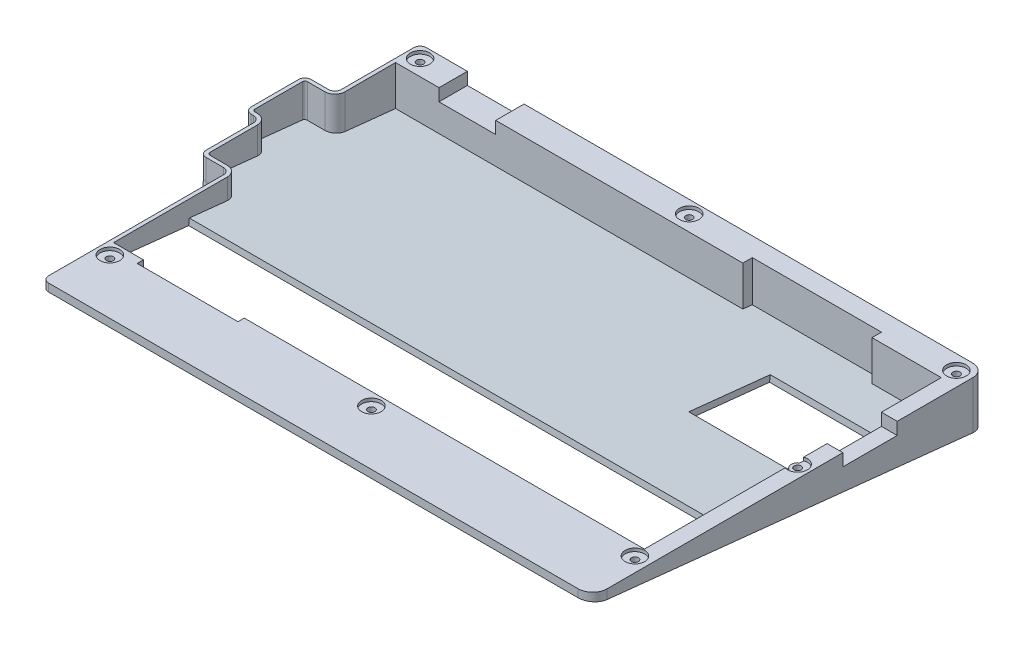
SolidWorks part; units mm, degrees
ref_plane "Front Plane" through (0, 0, 0) normal (0, 0, 1) x (1, 0, 0)
ref_plane "Top Plane" through (0, 0, 0) normal (0, 1, 0) x (1, 0, 0)
ref_plane "Right Plane" through (0, 0, 0) normal (1, 0, 0) x (0, 0, -1)
sketch "Sketch1" plane through (0, 0, 0) normal (0, 1, 0) x (1, 0, 0)
  line L0 (138.4196, 31.7518) -> (125.4196, 31.7518)
  line L1 (-35.0204, 31.7518) -> (107.4196, 31.7518)
  line L2 (140.4196, 29.7518) -> (140.4196, 6.7018)
  line L3 (-34.0204, 3.7518) -> (-34.0204, 22.7518)
  line L4 (136.4596, 27.7518) -> (136.4396, 27.7518)
  line L5 (142.4196, 4.7018) -> (147.9496, 4.7018)
  line L6 (-34.0204, 22.7518) -> (-12.0204, 22.7518)
  line L8 (149.9496, 2.7018) -> (149.9496, -12.3482)
  line L11 (147.9496, -14.3482) -> (147.1896, -14.3482)
  line L14 (145.1896, -16.3482) -> (145.1896, -31.3982)
  line L17 (143.1896, -33.3982) -> (137.6696, -33.3982)
  line L20 (135.6696, -35.3982) -> (135.6696, -77.4982)
  line L21 (-34.0204, -25.6003) -> (-34.0204, -71.4982)
  line L23 (133.6696, -79.4982) -> (-35.0204, -79.4982)
  line L28 (-39.0204, 27.7518) -> (-39.0204, 3.7518)
  line L31 (-34.0204, 3.7518) -> (-39.0204, 3.7518)
  line L32 (-34.0204, -13.4982) -> (-39.0204, -13.4982)
  line L33 (-39.0204, -75.4982) -> (-39.0204, -13.4982)
  line L34 (-34.0204, -71.4982) -> (92.9796, -71.4982)
  line L35 (92.9796, -71.4982) -> (92.9796, -73.4982)
  line L36 (92.9796, -73.4982) -> (124.9796, -73.4982)
  line L37 (124.9796, -73.4982) -> (124.9796, -71.4982)
  line L39 (134.4706, -35.3982) -> (134.4706, -71.4982)
  line L40 (134.4706, -71.4982) -> (124.9796, -71.4982)
  line L41 (137.6696, -32.1992) -> (143.1896, -32.1992)
  line L42 (-34.0204, -13.4982) -> (-34.0204, -22.1362)
  line L43 (143.9906, -31.3982) -> (143.9906, -16.3482)
  line L44 (-12.0204, 22.7518) -> (-12.0204, 25.7518)
  line L45 (147.1896, -13.1492) -> (147.9496, -13.1492)
  line L46 (148.7506, -12.3482) -> (148.7506, 2.7018)
  line L47 (-12.0204, 25.7518) -> (28.9796, 25.7518)
  line L48 (28.9796, 25.7518) -> (28.9796, 22.7518)
  line L49 (28.9796, 22.7518) -> (107.4196, 22.7518)
  line L50 (147.9496, 3.5027) -> (142.4196, 3.5027)
  line L51 (107.4196, 22.7518) -> (107.4196, 31.7518)
  line L52 (139.2206, 6.7018) -> (139.2206, 22.7518)
  line L53 (125.4196, 31.7518) -> (125.4196, 22.7518)
  line L54 (139.2206, 22.7518) -> (125.4196, 22.7518)
  arc A0 (138.4196, 31.7518) -> (140.4196, 29.7518) centre (138.4196, 29.7518) cw
  arc A1 (140.4196, 6.7018) -> (142.4196, 4.7018) centre (142.4196, 6.7018) ccw
  arc A2 (149.9496, 2.7018) -> (147.9496, 4.7018) centre (147.9496, 2.7018) ccw
  arc A3 (149.9496, -12.3482) -> (147.9496, -14.3482) centre (147.9496, -12.3482) cw
  arc A4 (147.1896, -14.3482) -> (145.1896, -16.3482) centre (147.1896, -16.3482) ccw
  arc A5 (145.1896, -31.3982) -> (143.1896, -33.3982) centre (143.1896, -31.3982) cw
  arc A6 (-35.0204, 31.7518) -> (-39.0204, 27.7518) centre (-35.0204, 27.7518) ccw
  arc A7 (-39.0204, -75.4982) -> (-35.0204, -79.4982) centre (-35.0204, -75.4982) ccw
  arc A8 (133.6696, -79.4982) -> (135.6696, -77.4982) centre (133.6696, -77.4982) ccw
  arc A9 (135.6696, -35.3982) -> (137.6696, -33.3982) centre (137.6696, -35.3982) cw
  circle A10 centre (-34.4204, 27.1518) radius 1.1
  circle A11 centre (51.0096, 27.7518) radius 1.1
  circle A12 centre (136.4396, 27.7518) radius 1.1
  circle A13 centre (-34.4204, -74.8982) radius 1.1
  circle A14 centre (48.6296, -75.4982) radius 1.1
  circle A15 centre (131.6496, -75.4982) radius 1.1
  circle A16 centre (-35.0204, -23.8682) radius 1.1
  arc A27 (-34.0204, -22.1362) -> (-34.0204, -25.6003) centre (-35.0204, -23.8682) cw
  arc A28 (139.2206, 6.7018) -> (142.4196, 3.5027) centre (142.4196, 6.7018) ccw
  arc A29 (147.9496, 3.5027) -> (148.7506, 2.7018) centre (147.9496, 2.7018) cw
  arc A30 (148.7506, -12.3482) -> (147.9496, -13.1492) centre (147.9496, -12.3482) cw
  arc A31 (147.1896, -13.1492) -> (143.9906, -16.3482) centre (147.1896, -16.3482) ccw
  arc A32 (143.9906, -31.3982) -> (143.1896, -32.1992) centre (143.1896, -31.3982) cw
  arc A33 (137.6696, -32.1992) -> (134.4706, -35.3982) centre (137.6696, -35.3982) ccw
extrude "Boss-Extrude2" add sketch "Sketch1" against normal blind 4.7 contours L41 A33 L39 L40 L37 L36 L35 L34 L21 A27 L42 L32 L33 A7 L23 A8 L20 A9 L17 A5 L14 A4 L11 A3 L8 A2 L5 A1 L2 A0 L0 L53 L54 L52 A28 L50 A29 L46 A30 L45 A31 L43 A32 A12 A13 A14 A15 | L1 A6 L28 L31 L3 L6 L44 L47 L48 L49 L51 A11 A10 region at (138.2833, 0, -29.6154) region at (31.7683, 0, -26.4895)
move or copy body "Body-Move/Copy1" bodies to move or copy 105 104 copy no rotation origin (55.4646, -2.35, 0) rotation axis (0, 0, 1) rotation angle 180
sketch "Sketch3" plane through (149.9496, 0, 0) normal (1, 0, 0) x (0, 0, -1)
  line L0 (-79.4982, 0) -> (-79.4982, -4.7) construction
  line L1 (-79.4982, 0) -> (-79.4982, -4.7)
  line L2 (31.7518, 0) -> (31.7518, -4.7) construction
  line L3 (31.7518, 0) -> (31.7518, -4.7)
  line L5 (-79.4982, -4.7) -> (31.7518, -16.3928)
  line L6 (31.7518, -16.3928) -> (31.7518, -4.7)
  line L7 (31.7518, -4.7) -> (-79.4982, -4.7)
  line M3 (-75.4982, -4.7) -> (-13.4982, -4.7)
  dimension "D1" = 6
extrude "Boss-Extrude3" add sketch "Sketch3" against normal up to surface (188.97 mm away) contours L6 L7 L5 M3 region at (149.9496, -8.5976, 5.3315) up to face at (-39.0204, -2.35, 4.8232)
sketch "Sketch4" plane through (0, -4.7, 0) normal (0, 1, 0) x (1, 0, 0)
  line L2 (145.9496, -79.4982) -> (149.9496, -79.4982)
  line L3 (149.9496, -79.4982) -> (149.9496, -75.4982)
  line L4 (-29.4904, 6.7018) -> (-29.4904, 29.7518)
  line L5 (-27.4904, 31.7518) -> (-39.0204, 31.7518)
  line L6 (-36.2604, -14.3482) -> (-37.0204, -14.3482)
  line L7 (-39.0204, -12.3482) -> (-39.0204, -79.4982)
  line L8 (-39.0204, -79.4982) -> (-22.7404, -79.4982)
  line L9 (-24.7404, -77.4982) -> (-24.7404, -35.3982)
  line L10 (-26.7404, -33.3982) -> (-32.2604, -33.3982)
  line L11 (-34.2604, -31.3982) -> (-34.2604, -16.3482)
  line L12 (-36.2604, -14.3482) -> (-37.0204, -14.3482)
  line L13 (-39.0204, -12.3482) -> (-39.0204, -79.4982)
  line L14 (-39.0204, -79.4982) -> (-22.7404, -79.4982)
  line L15 (-24.7404, -77.4982) -> (-24.7404, -35.3982)
  line L16 (-26.7404, -33.3982) -> (-32.2604, -33.3982)
  line L17 (-34.2604, -31.3982) -> (-34.2604, -16.3482)
  line L18 (-39.0204, 31.7518) -> (-39.0204, 2.7018)
  line L19 (-37.0204, 4.7018) -> (-31.4904, 4.7018)
  line L20 (-29.4904, 6.7018) -> (-29.4904, 29.7518)
  line L21 (-27.4904, 31.7518) -> (-39.0204, 31.7518)
  line L22 (-39.0204, 31.7518) -> (-39.0204, 2.7018)
  line L23 (-37.0204, 4.7018) -> (-31.4904, 4.7018)
  line L24 (145.9496, -79.4982) -> (149.9496, -79.4982)
  line L25 (149.9496, -79.4982) -> (149.9496, -75.4982)
  line L26 (149.9496, 31.7518) -> (145.9496, 31.7518)
  line L27 (149.9496, 27.7518) -> (149.9496, 31.7518)
  line L28 (149.9496, 31.7518) -> (145.9496, 31.7518)
  line L29 (149.9496, 27.7518) -> (149.9496, 31.7518)
  arc A1 (145.9496, -79.4982) -> (149.9496, -75.4982) centre (145.9496, -75.4982) ccw
  arc A2 (145.9496, -79.4982) -> (149.9496, -75.4982) centre (145.9496, -75.4982) ccw
  arc A3 (-27.4904, 31.7518) -> (-29.4904, 29.7518) centre (-27.4904, 29.7518) ccw
  arc A4 (-37.0204, 4.7018) -> (-39.0204, 2.7018) centre (-37.0204, 2.7018) ccw
  arc A5 (-39.0204, -12.3482) -> (-37.0204, -14.3482) centre (-37.0204, -12.3482) ccw
  arc A6 (-24.7404, -77.4982) -> (-22.7404, -79.4982) centre (-22.7404, -77.4982) ccw
  arc A7 (-24.7404, -35.3982) -> (-26.7404, -33.3982) centre (-26.7404, -35.3982) ccw
  arc A8 (-34.2604, -31.3982) -> (-32.2604, -33.3982) centre (-32.2604, -31.3982) ccw
  arc A9 (-34.2604, -16.3482) -> (-36.2604, -14.3482) centre (-36.2604, -16.3482) ccw
  arc A10 (-39.0204, -12.3482) -> (-37.0204, -14.3482) centre (-37.0204, -12.3482) ccw
  arc A11 (-24.7404, -77.4982) -> (-22.7404, -79.4982) centre (-22.7404, -77.4982) ccw
  arc A12 (-24.7404, -35.3982) -> (-26.7404, -33.3982) centre (-26.7404, -35.3982) ccw
  arc A13 (-34.2604, -31.3982) -> (-32.2604, -33.3982) centre (-32.2604, -31.3982) ccw
  arc A14 (-34.2604, -16.3482) -> (-36.2604, -14.3482) centre (-36.2604, -16.3482) ccw
  arc A15 (-31.4904, 4.7018) -> (-29.4904, 6.7018) centre (-31.4904, 6.7018) ccw
  arc A16 (-27.4904, 31.7518) -> (-29.4904, 29.7518) centre (-27.4904, 29.7518) ccw
  arc A17 (-37.0204, 4.7018) -> (-39.0204, 2.7018) centre (-37.0204, 2.7018) ccw
  arc A18 (-31.4904, 4.7018) -> (-29.4904, 6.7018) centre (-31.4904, 6.7018) ccw
  arc A19 (149.9496, 27.7518) -> (145.9496, 31.7518) centre (145.9496, 27.7518) ccw
  arc A20 (149.9496, 27.7518) -> (145.9496, 31.7518) centre (145.9496, 27.7518) ccw
  dimension "D1" = 0
  dimension "D2" = 0
  dimension "D3" = 0
  dimension "D4" = 0
extrude "Cut-Extrude1" cut sketch "Sketch4" against normal through all
ref_plane "Plane4" through (0, 15, 0) normal (0, 1, 0) x (1, 0, 0)
sketch "Sketch10" plane through (0, 15, 0) normal (0, 1, 0) x (1, 0, 0)
  line L0 (-14.4904, 22.7518) -> (3.5096, 22.7518)
  line L1 (144.9496, 3.7518) -> (144.9496, -13.4982)
  line L27 (-14.4904, 31.7518) -> (-14.4904, 22.7518)
  line L28 (-14.4904, 22.7518) -> (-28.2913, 22.7518)
  line L29 (-28.2913, 22.7518) -> (-28.2913, 6.7018)
  line L30 (-31.4904, 3.5027) -> (-37.0204, 3.5027)
  line L31 (-37.8213, 2.7018) -> (-37.8213, -12.3482)
  line L32 (-37.0204, -13.1492) -> (-36.2604, -13.1492)
  line L33 (-33.0613, -16.3482) -> (-33.0613, -31.3982)
  line L34 (-32.2604, -32.1992) -> (-26.7404, -32.1992)
  line L35 (-23.5413, -35.3982) -> (-23.5413, -71.4982)
  line L36 (-23.5413, -71.4982) -> (-14.0504, -71.4982)
  line L37 (-14.0504, -71.4982) -> (-14.0504, -73.4982)
  line L38 (-14.0504, -73.4982) -> (17.9496, -73.4982)
  line L39 (17.9496, -73.4982) -> (17.9496, -71.4982)
  line L40 (17.9496, -71.4982) -> (144.9496, -71.4982)
  line L41 (144.9496, -71.4982) -> (144.9496, -25.6003)
  line L42 (144.9496, -22.1362) -> (144.9496, -13.4982)
  line L43 (144.9496, -13.4982) -> (149.9496, -13.4982)
  line L44 (149.9496, -13.4982) -> (149.9496, 3.7518)
  line L45 (149.9496, 3.7518) -> (144.9496, 3.7518)
  line L46 (144.9496, 3.7518) -> (144.9496, 22.7518)
  line L47 (144.9496, 22.7518) -> (122.9496, 22.7518)
  line L48 (122.9496, 22.7518) -> (122.9496, 25.7518)
  line L49 (122.9496, 25.7518) -> (81.9496, 25.7518)
  line L50 (81.9496, 25.7518) -> (81.9496, 22.7518)
  line L51 (81.9496, 22.7518) -> (3.5096, 22.7518)
  line L52 (3.5096, 22.7518) -> (3.5096, 31.7518)
  line L53 (3.5096, 31.7518) -> (-14.4904, 31.7518)
  line L54 (-14.4904, 31.7518) -> (-14.4904, 22.7518)
  line L55 (-14.4904, 22.7518) -> (-28.2913, 22.7518)
  line L56 (-28.2913, 22.7518) -> (-28.2913, 6.7018)
  line L57 (-31.4904, 3.5027) -> (-37.0204, 3.5027)
  line L58 (-37.8213, 2.7018) -> (-37.8213, -12.3482)
  line L59 (-37.0204, -13.1492) -> (-36.2604, -13.1492)
  line L60 (-33.0613, -16.3482) -> (-33.0613, -31.3982)
  line L61 (-32.2604, -32.1992) -> (-26.7404, -32.1992)
  line L62 (-23.5413, -35.3982) -> (-23.5413, -71.4982)
  line L63 (-23.5413, -71.4982) -> (-14.0504, -71.4982)
  line L64 (-14.0504, -71.4982) -> (-14.0504, -73.4982)
  line L65 (-14.0504, -73.4982) -> (17.9496, -73.4982)
  line L66 (17.9496, -73.4982) -> (17.9496, -71.4982)
  line L67 (17.9496, -71.4982) -> (144.9496, -71.4982)
  line L68 (144.9496, -71.4982) -> (144.9496, -25.6003)
  line L69 (144.9496, -22.1362) -> (144.9496, -13.4982)
  line L70 (144.9496, -13.4982) -> (149.9496, -13.4982)
  line L71 (149.9496, -13.4982) -> (149.9496, 3.7518)
  line L72 (149.9496, 3.7518) -> (144.9496, 3.7518)
  line L73 (144.9496, 3.7518) -> (144.9496, 22.7518)
  line L74 (144.9496, 22.7518) -> (122.9496, 22.7518)
  line L75 (122.9496, 22.7518) -> (122.9496, 25.7518)
  line L76 (122.9496, 25.7518) -> (81.9496, 25.7518)
  line L77 (81.9496, 25.7518) -> (81.9496, 22.7518)
  line L78 (81.9496, 22.7518) -> (3.5096, 22.7518)
  line L79 (3.5096, 22.7518) -> (3.5096, 31.7518)
  line L80 (3.5096, 31.7518) -> (-14.4904, 31.7518)
  arc A7 (-31.4904, 3.5027) -> (-28.2913, 6.7018) centre (-31.4904, 6.7018) ccw
  arc A8 (-37.0204, 3.5027) -> (-37.8213, 2.7018) centre (-37.0204, 2.7018) ccw
  arc A9 (-37.8213, -12.3482) -> (-37.0204, -13.1492) centre (-37.0204, -12.3482) ccw
  arc A10 (-33.0613, -16.3482) -> (-36.2604, -13.1492) centre (-36.2604, -16.3482) ccw
  arc A11 (-33.0613, -31.3982) -> (-32.2604, -32.1992) centre (-32.2604, -31.3982) ccw
  arc A12 (-23.5413, -35.3982) -> (-26.7404, -32.1992) centre (-26.7404, -35.3982) ccw
  arc A13 (144.9496, -22.1362) -> (144.9496, -25.6003) centre (145.9496, -23.8682) ccw
  arc A14 (-31.4904, 3.5027) -> (-28.2913, 6.7018) centre (-31.4904, 6.7018) ccw
  arc A15 (-37.0204, 3.5027) -> (-37.8213, 2.7018) centre (-37.0204, 2.7018) ccw
  arc A16 (-37.8213, -12.3482) -> (-37.0204, -13.1492) centre (-37.0204, -12.3482) ccw
  arc A17 (-33.0613, -16.3482) -> (-36.2604, -13.1492) centre (-36.2604, -16.3482) ccw
  arc A18 (-33.0613, -31.3982) -> (-32.2604, -32.1992) centre (-32.2604, -31.3982) ccw
  arc A19 (-23.5413, -35.3982) -> (-26.7404, -32.1992) centre (-26.7404, -35.3982) ccw
  arc A20 (144.9496, -22.1362) -> (144.9496, -25.6003) centre (145.9496, -23.8682) ccw
  dimension "D1" = 0
extrude "Cut-Extrude2" cut sketch "Sketch10" against normal through all contours A20 L69 L1 L73 L74 L75 L76 L77 L78 L0 L55 L56 A14 L57 A15 L58 A16 L59 A17 L60 A18 L61 A19 L62 L63 L64 L65 L66 L67 L68 region at (57.9798, 15, 23.6888)
sketch "Sketch11" plane through (144.9496, 0, 0) normal (-1, 0, 0) x (0, 0, 1)
  line L0 (-22.7518, -15.4469) -> (71.4982, -5.5408)
  line L1 (71.4982, -5.5408) -> (71.4982, -3.5408)
  line L2 (71.4982, 0) -> (71.4982, -5.5408) construction
  line L3 (71.4982, -3.5408) -> (-22.7518, -13.4469)
  line L4 (-22.7518, 0) -> (-22.7518, -15.4469) construction
  line L5 (-22.7518, -13.4469) -> (-22.7518, -15.4469)
  dimension "D1" = 2
  dimension "D2" = 2
extrude "Boss-Extrude4" add sketch "Sketch11" along normal up to surface (182.7709 mm away)
sketch "Sketch12" plane through (0, -10.9348, 1.1493) normal (0, 0.9945, -0.1045) x (1, 0, 0)
  line L0 (-29.4904, 7.8943) -> (-29.4904, 24.0327) construction
  line L1 (-29.4904, 24.0327) -> (-37.8213, 24.0327) construction
  line L2 (-37.8213, 24.0327) -> (-37.8213, 5.715) construction
  line L3 (-37.0204, 5.8833) -> (-31.4904, 5.8833) construction
  line L4 (-36.2604, -13.2716) -> (-37.0204, -13.2716) construction
  line L5 (-37.8213, -13.1033) -> (-37.8213, -70.7364) construction
  line L6 (-37.8213, -70.7364) -> (-24.7404, -70.7364) construction
  line L7 (-24.7404, -70.7364) -> (-24.7404, -34.4376) construction
  line L8 (-26.7404, -32.4266) -> (-32.2604, -32.4266) construction
  line L9 (-34.2604, -30.4155) -> (-34.2604, -15.2826) construction
  line L10 (-29.4904, 7.8943) -> (-29.4904, 24.0327)
  line L11 (-29.4904, 24.0327) -> (-37.8213, 24.0327)
  line L12 (-37.8213, 24.0327) -> (-37.8213, 5.715)
  line L13 (-37.0204, 5.8833) -> (-31.4904, 5.8833)
  line L14 (-36.2604, -13.2716) -> (-37.0204, -13.2716)
  line L15 (-37.8213, -13.1033) -> (-37.8213, -70.7364)
  line L16 (-37.8213, -70.7364) -> (-24.7404, -70.7364)
  line L17 (-24.7404, -70.7364) -> (-24.7404, -34.4376)
  line L18 (-26.7404, -32.4266) -> (-32.2604, -32.4266)
  line L19 (-34.2604, -30.4155) -> (-34.2604, -15.2826)
  line L20 (-37.8213, 24.0327) -> (-37.8213, 25.9101)
  line L21 (-29.4904, 24.0327) -> (-29.4904, 27.1127)
  line L22 (-29.4904, 27.1127) -> (-37.8213, 25.9101)
  ellipse E0 centre (-31.4904, 7.8943) end of major axis (-31.4904, 9.9053) minor radius 2 (-31.4904, 5.8833) -> (-29.4904, 7.8943) ccw construction
  ellipse E1 centre (-37.0204, 3.8723) end of major axis (-37.0204, 5.8833) minor radius 2 (-37.0204, 5.8833) -> (-37.8213, 5.715) ccw construction
  ellipse E2 centre (-37.0204, -11.2606) end of major axis (-37.0204, -9.2496) minor radius 2 (-37.8213, -13.1033) -> (-37.0204, -13.2716) ccw construction
  ellipse E3 centre (-26.7404, -34.4376) end of major axis (-26.7404, -32.4266) minor radius 2 (-24.7404, -34.4376) -> (-26.7404, -32.4266) ccw construction
  ellipse E4 centre (-32.2604, -30.4155) end of major axis (-32.2604, -28.4045) minor radius 2 (-34.2604, -30.4155) -> (-32.2604, -32.4266) ccw construction
  ellipse E5 centre (-36.2604, -15.2826) end of major axis (-36.2604, -13.2716) minor radius 2 (-34.2604, -15.2826) -> (-36.2604, -13.2716) ccw construction
  ellipse E6 centre (-31.4904, 7.8943) end of major axis (-31.4904, 9.9053) minor radius 2 (-31.4904, 5.8833) -> (-29.4904, 7.8943) ccw
  ellipse E7 centre (-37.0204, 3.8723) end of major axis (-37.0204, 5.8833) minor radius 2 (-37.0204, 5.8833) -> (-37.8213, 5.715) ccw
  ellipse E8 centre (-37.0204, -11.2606) end of major axis (-37.0204, -9.2496) minor radius 2 (-37.8213, -13.1033) -> (-37.0204, -13.2716) ccw
  ellipse E9 centre (-26.7404, -34.4376) end of major axis (-26.7404, -32.4266) minor radius 2 (-24.7404, -34.4376) -> (-26.7404, -32.4266) ccw
  ellipse E10 centre (-32.2604, -30.4155) end of major axis (-32.2604, -28.4045) minor radius 2 (-34.2604, -30.4155) -> (-32.2604, -32.4266) ccw
  ellipse E11 centre (-36.2604, -15.2826) end of major axis (-36.2604, -13.2716) minor radius 2 (-34.2604, -15.2826) -> (-36.2604, -13.2716) ccw
sketch "Sketch26" plane through (-37.8213, 0, 0) normal (-1, 0, 0) x (0, 0, 1)
  line L0 (14.1808, -9.5651) -> (-4.5344, -11.5322)
  line L1 (-4.5344, -13.5322) -> (14.1808, -11.5651)
  line L4 (-22.7518, -15.4469) -> (-4.5344, -13.5322)
  line L5 (-4.5344, -13.5322) -> (-4.5344, -11.5322)
  line L6 (-4.5344, -11.5322) -> (-22.7518, -13.4469)
  line L7 (-22.7518, -13.4469) -> (-22.7518, -15.4469)
  line L8 (-22.7518, -15.4469) -> (-4.5344, -13.5322)
  line L9 (-4.5344, -13.5322) -> (-4.5344, -11.5322)
  line L10 (-4.5344, -11.5322) -> (-22.7518, -13.4469)
  line L11 (-22.7518, -13.4469) -> (-22.7518, -15.4469)
  line L12 (14.1808, -9.5651) -> (14.1808, -11.5651)
  line L13 (14.1808, -11.5651) -> (71.4982, -5.5408)
  line L14 (71.4982, -5.5408) -> (71.4982, -3.5408)
  line L15 (71.4982, -3.5408) -> (14.1808, -9.5651)
  line L16 (14.1808, -9.5651) -> (14.1808, -11.5651)
  line L17 (14.1808, -11.5651) -> (71.4982, -5.5408)
  line L18 (71.4982, -5.5408) -> (71.4982, -3.5408)
  line L19 (71.4982, -3.5408) -> (14.1808, -9.5651)
  line M9 (14.1808, -9.5651) -> (14.1808, -11.5651)
  line M10 (14.1808, -11.5651) -> (71.4982, -5.5408)
  line M11 (71.4982, -5.5408) -> (71.4982, -3.5408)
  line M12 (71.4982, -3.5408) -> (14.1808, -9.5651)
  dimension "D1" = 0
  dimension "D2" = 0
extrude "Boss-Extrude10" add sketch "Sketch26" along normal blind 11 contours L10 L11 L8 L9 | L9 L1 L0 M9 | M12 M9 M10 M11 region at (-37.8213, -11.5487, 4.8232) region at (-37.8213, -7.553, 42.8395) region at (-37.8213, -13.4895, -13.6431)
sketch "Sketch28" plane through (0, -10.9348, 1.1493) normal (0, 0.9945, -0.1045) x (1, 0, 0)
  line L0 (-48.8213, 24.0327) -> (-52.7132, 28.3929)
  line L1 (-52.7132, 28.3929) -> (-29.4904, 30.8021)
  line L2 (-29.4904, 30.8021) -> (-29.4904, 24.0327)
  line L10 (-29.4904, 7.8943) -> (-29.4904, 24.0327)
  line L11 (-29.4904, 24.0327) -> (-48.8213, 24.0327)
  line L12 (-48.8213, 24.0327) -> (-48.8213, -70.7364)
  line L13 (-48.8213, -70.7364) -> (-24.7404, -70.7364)
  line L14 (-24.7404, -70.7364) -> (-24.7404, -34.4376)
  line L15 (-26.7404, -32.4266) -> (-32.2604, -32.4266)
  line L16 (-34.2604, -30.4155) -> (-34.2604, -15.2826)
  line L17 (-36.2604, -13.2716) -> (-37.0204, -13.2716)
  line L18 (-39.0204, -11.2606) -> (-39.0204, 3.8723)
  line L19 (-37.0204, 5.8833) -> (-31.4904, 5.8833)
  line L20 (-29.4904, 7.8943) -> (-29.4904, 24.0327)
  line L21 (-29.4904, 24.0327) -> (-48.8213, 24.0327)
  line L22 (-48.8213, 24.0327) -> (-48.8213, -70.7364)
  line L23 (-48.8213, -70.7364) -> (-24.7404, -70.7364)
  line L24 (-24.7404, -70.7364) -> (-24.7404, -34.4376)
  line L25 (-26.7404, -32.4266) -> (-32.2604, -32.4266)
  line L26 (-34.2604, -30.4155) -> (-34.2604, -15.2826)
  line L27 (-36.2604, -13.2716) -> (-37.0204, -13.2716)
  line L28 (-39.0204, -11.2606) -> (-39.0204, 3.8723)
  line L29 (-37.0204, 5.8833) -> (-31.4904, 5.8833)
  ellipse E6 centre (-31.4904, 7.8943) end of major axis (-31.4904, 9.9053) minor radius 2 (-31.4904, 5.8833) -> (-29.4904, 7.8943) ccw
  ellipse E7 centre (-26.7404, -34.4376) end of major axis (-26.7404, -32.4266) minor radius 2 (-24.7404, -34.4376) -> (-26.7404, -32.4266) ccw
  ellipse E8 centre (-32.2604, -30.4155) end of major axis (-32.2604, -28.4045) minor radius 2 (-34.2604, -30.4155) -> (-32.2604, -32.4266) ccw
  ellipse E9 centre (-36.2604, -15.2826) end of major axis (-36.2604, -13.2716) minor radius 2 (-34.2604, -15.2826) -> (-36.2604, -13.2716) ccw
  ellipse E10 centre (-37.0204, -11.2606) end of major axis (-37.0204, -9.2496) minor radius 2 (-39.0204, -11.2606) -> (-37.0204, -13.2716) ccw
  ellipse E11 centre (-37.0204, 3.8723) end of major axis (-37.0204, 5.8833) minor radius 2 (-37.0204, 5.8833) -> (-39.0204, 3.8723) ccw
  ellipse E12 centre (-31.4904, 7.8943) end of major axis (-31.4904, 9.9053) minor radius 2 (-31.4904, 5.8833) -> (-29.4904, 7.8943) ccw
  ellipse E13 centre (-26.7404, -34.4376) end of major axis (-26.7404, -32.4266) minor radius 2 (-24.7404, -34.4376) -> (-26.7404, -32.4266) ccw
  ellipse E14 centre (-32.2604, -30.4155) end of major axis (-32.2604, -28.4045) minor radius 2 (-34.2604, -30.4155) -> (-32.2604, -32.4266) ccw
  ellipse E15 centre (-36.2604, -15.2826) end of major axis (-36.2604, -13.2716) minor radius 2 (-34.2604, -15.2826) -> (-36.2604, -13.2716) ccw
  ellipse E16 centre (-37.0204, -11.2606) end of major axis (-37.0204, -9.2496) minor radius 2 (-39.0204, -11.2606) -> (-37.0204, -13.2716) ccw
  ellipse E17 centre (-37.0204, 3.8723) end of major axis (-37.0204, 5.8833) minor radius 2 (-37.0204, 5.8833) -> (-39.0204, 3.8723) ccw
  ellipse M17 centre (-31.4904, 7.8943) end of major axis (-31.4904, 9.9053) minor radius 2 (-31.4904, 5.8833) -> (-29.4904, 7.8943) ccw
  line M18 (-29.4904, 7.8943) -> (-29.4904, 24.0327)
  line M19 (-29.4904, 24.0327) -> (-48.8213, 24.0327)
  line M20 (-48.8213, 24.0327) -> (-48.8213, -70.7364)
  line M21 (-48.8213, -70.7364) -> (-24.7404, -70.7364)
  line M22 (-24.7404, -70.7364) -> (-24.7404, -34.4376)
  ellipse M23 centre (-26.7404, -34.4376) end of major axis (-26.7404, -32.4266) minor radius 2 (-24.7404, -34.4376) -> (-26.7404, -32.4266) ccw
  line M24 (-26.7404, -32.4266) -> (-32.2604, -32.4266)
  ellipse M25 centre (-32.2604, -30.4155) end of major axis (-32.2604, -28.4045) minor radius 2 (-32.2604, -32.4266) -> (-34.2604, -30.4155) cw
  line M26 (-34.2604, -30.4155) -> (-34.2604, -15.2826)
  ellipse M27 centre (-36.2604, -15.2826) end of major axis (-36.2604, -13.2716) minor radius 2 (-34.2604, -15.2826) -> (-36.2604, -13.2716) ccw
  line M28 (-36.2604, -13.2716) -> (-37.0204, -13.2716)
  ellipse M29 centre (-37.0204, -11.2606) end of major axis (-37.0204, -9.2496) minor radius 2 (-37.0204, -13.2716) -> (-39.0204, -11.2606) cw
  line M30 (-39.0204, -11.2606) -> (-39.0204, 3.8723)
  ellipse M31 centre (-37.0204, 3.8723) end of major axis (-37.0204, 5.8833) minor radius 2 (-39.0204, 3.8723) -> (-37.0204, 5.8833) cw
  line M32 (-37.0204, 5.8833) -> (-31.4904, 5.8833)
  dimension "D1" = 0
extrude "Cut-Extrude8" cut sketch "Sketch28" against normal blind 11 contours M32 M17 M18 M19 M20 M21 M22 M23 M24 M25 M26 M27 M28 M29 M30 M31 | L2 L1 L0 M19 region at (-39.4803, -13.7524, -25.6581) region at (-38.8035, -7.967, 29.3861)
sketch "Sketch30" plane through (122.9496, 0, 0) normal (-1, 0, 0) x (0, 0, 1)
  line L0 (-25.7518, -15.7622) -> (-22.7518, -15.4469)
  line L1 (-22.7518, -15.4469) -> (-22.7518, -13.4469)
  line L2 (-22.7518, -15.4469) -> (-22.7518, -13.4469) construction
  line L3 (-22.7518, -13.4469) -> (-25.7518, -13.7622)
  line L4 (-25.7518, 0) -> (-25.7518, -15.7622) construction
  line L5 (-25.7518, -13.7622) -> (-25.7518, -15.7622)
extrude "Boss-Extrude11" add sketch "Sketch30" along normal up to surface (41 mm away)
sketch "Sketch32" plane through (17.9496, 0, 0) normal (-1, 0, 0) x (0, 0, 1)
  line L0 (73.4982, -5.3306) -> (71.4982, -5.5408)
  line L1 (71.4982, -5.5408) -> (71.4982, -3.5408)
  line L2 (71.4982, -3.5408) -> (73.4982, -3.3306)
  line L3 (73.4982, 0) -> (73.4982, -5.3306) construction
  line L4 (73.4982, -3.3306) -> (73.4982, -5.3306)
  dimension "D1" = 2
extrude "Boss-Extrude14" add sketch "Sketch32" along normal up to surface (32 mm away)
sketch "Sketch35" plane through (0, 0, 0) normal (0, 1, 0) x (1, 0, 0)
  line L0 (149.9496, 3.7518) -> (149.9496, -13.4982)
  line L1 (149.9496, -13.4982) -> (144.9496, -13.4982)
  line L2 (144.9496, -13.4982) -> (144.9496, 3.7518)
  line L3 (144.9496, 3.7518) -> (149.9496, 3.7518)
ref_plane "Plane5" through (149.9496, -5.1204, 75.4982) normal (0, -1, 0) x (-1, 0, 0)
sketch "Sketch47" plane through (0, 0, 0) normal (0, 1, 0) x (1, 0, 0)
  circle A0 centre (145.3496, -74.8982) radius 3.1
  circle A1 centre (62.2996, -75.4982) radius 3.1
  circle A2 centre (-20.7204, -75.4982) radius 3.1
  circle A3 centre (-25.5104, 27.7518) radius 3.1
  circle A4 centre (59.9196, 27.7518) radius 3.1
  circle A5 centre (145.3496, 27.1518) radius 3.1
  circle A6 centre (145.9496, -23.8682) radius 3.1
extrude "Cut-Extrude17" cut sketch "Sketch47" against normal blind 1.8
sketch "Sketch48" plane through (0, 0, 0) normal (0, 1, 0) x (1, 0, 0)
  line L10 (145.9496, 31.7518) -> (3.5096, 31.7518)
  line L11 (3.5096, 31.7518) -> (3.5096, 22.7518)
  line L12 (3.5096, 22.7518) -> (81.9496, 22.7518)
  line L13 (81.9496, 22.7518) -> (81.9496, 25.7518)
  line L14 (81.9496, 25.7518) -> (122.9496, 25.7518)
  line L15 (122.9496, 25.7518) -> (122.9496, 22.7518)
  line L16 (122.9496, 22.7518) -> (144.9496, 22.7518)
  line L17 (144.9496, 22.7518) -> (144.9496, 3.7518)
  line L18 (144.9496, 3.7518) -> (149.9496, 3.7518)
  line L19 (149.9496, 3.7518) -> (149.9496, 27.7518)
  line L20 (145.9496, 31.7518) -> (3.5096, 31.7518)
  line L21 (3.5096, 31.7518) -> (3.5096, 22.7518)
  line L22 (3.5096, 22.7518) -> (81.9496, 22.7518)
  line L23 (81.9496, 22.7518) -> (81.9496, 25.7518)
  line L24 (81.9496, 25.7518) -> (122.9496, 25.7518)
  line L25 (122.9496, 25.7518) -> (122.9496, 22.7518)
  line L26 (122.9496, 22.7518) -> (144.9496, 22.7518)
  line L27 (144.9496, 22.7518) -> (144.9496, 3.7518)
  line L28 (144.9496, 3.7518) -> (149.9496, 3.7518)
  line L29 (149.9496, 3.7518) -> (149.9496, 27.7518)
  line L47 (144.9496, -13.4982) -> (144.9496, -20.9339)
  line L48 (144.9496, -26.8025) -> (144.9496, -71.4982)
  line L49 (144.9496, -71.4982) -> (17.9496, -71.4982)
  line L50 (17.9496, -71.4982) -> (17.9496, -73.4982)
  line L51 (17.9496, -73.4982) -> (-14.0504, -73.4982)
  line L52 (-14.0504, -73.4982) -> (-14.0504, -71.4982)
  line L53 (-14.0504, -71.4982) -> (-23.5413, -71.4982)
  line L54 (-23.5413, -71.4982) -> (-23.5413, -35.3982)
  line L55 (-26.7404, -32.1992) -> (-32.2604, -32.1992)
  line L56 (-33.0613, -31.3982) -> (-33.0613, -16.3482)
  line L57 (-36.2604, -13.1492) -> (-37.0204, -13.1492)
  line L58 (-37.8213, -12.3482) -> (-37.8213, 2.7018)
  line L59 (-37.0204, 3.5027) -> (-31.4904, 3.5027)
  line L60 (-28.2913, 6.7018) -> (-28.2913, 22.7518)
  line L61 (-28.2913, 22.7518) -> (-14.4904, 22.7518)
  line L62 (-14.4904, 22.7518) -> (-14.4904, 31.7518)
  line L63 (-14.4904, 31.7518) -> (-27.4904, 31.7518)
  line L64 (-29.4904, 29.7518) -> (-29.4904, 6.7018)
  line L65 (-31.4904, 4.7018) -> (-37.0204, 4.7018)
  line L66 (-39.0204, 2.7018) -> (-39.0204, -12.3482)
  line L67 (-37.0204, -14.3482) -> (-36.2604, -14.3482)
  line L68 (-34.2604, -16.3482) -> (-34.2604, -31.3982)
  line L69 (-32.2604, -33.3982) -> (-26.7404, -33.3982)
  line L70 (-24.7404, -35.3982) -> (-24.7404, -77.4982)
  line L71 (-22.7404, -79.4982) -> (145.9496, -79.4982)
  line L72 (149.9496, -75.4982) -> (149.9496, -13.4982)
  line L73 (149.9496, -13.4982) -> (144.9496, -13.4982)
  line L74 (144.9496, -13.4982) -> (144.9496, -20.9339)
  line L75 (144.9496, -26.8025) -> (144.9496, -71.4982)
  line L76 (144.9496, -71.4982) -> (17.9496, -71.4982)
  line L77 (17.9496, -71.4982) -> (17.9496, -73.4982)
  line L78 (17.9496, -73.4982) -> (-14.0504, -73.4982)
  line L79 (-14.0504, -73.4982) -> (-14.0504, -71.4982)
  line L80 (-14.0504, -71.4982) -> (-23.5413, -71.4982)
  line L81 (-23.5413, -71.4982) -> (-23.5413, -35.3982)
  line L82 (-26.7404, -32.1992) -> (-32.2604, -32.1992)
  line L83 (-33.0613, -31.3982) -> (-33.0613, -16.3482)
  line L84 (-36.2604, -13.1492) -> (-37.0204, -13.1492)
  line L85 (-37.8213, -12.3482) -> (-37.8213, 2.7018)
  line L86 (-37.0204, 3.5027) -> (-31.4904, 3.5027)
  line L87 (-28.2913, 6.7018) -> (-28.2913, 22.7518)
  line L88 (-28.2913, 22.7518) -> (-14.4904, 22.7518)
  line L89 (-14.4904, 22.7518) -> (-14.4904, 31.7518)
  line L90 (-14.4904, 31.7518) -> (-27.4904, 31.7518)
  line L91 (-29.4904, 29.7518) -> (-29.4904, 6.7018)
  line L92 (-31.4904, 4.7018) -> (-37.0204, 4.7018)
  line L93 (-39.0204, 2.7018) -> (-39.0204, -12.3482)
  line L94 (-37.0204, -14.3482) -> (-36.2604, -14.3482)
  line L95 (-34.2604, -16.3482) -> (-34.2604, -31.3982)
  line L96 (-32.2604, -33.3982) -> (-26.7404, -33.3982)
  line L97 (-24.7404, -35.3982) -> (-24.7404, -77.4982)
  line L98 (-22.7404, -79.4982) -> (145.9496, -79.4982)
  line L99 (149.9496, -75.4982) -> (149.9496, -13.4982)
  line L100 (149.9496, -13.4982) -> (144.9496, -13.4982)
  arc A1 (149.9496, 27.7518) -> (145.9496, 31.7518) centre (145.9496, 27.7518) ccw
  arc A2 (149.9496, 27.7518) -> (145.9496, 31.7518) centre (145.9496, 27.7518) ccw
  arc A18 (144.9496, -26.8025) -> (144.9496, -20.9339) centre (145.9496, -23.8682) ccw
  arc A19 (-23.5413, -35.3982) -> (-26.7404, -32.1992) centre (-26.7404, -35.3982) ccw
  arc A20 (-33.0613, -31.3982) -> (-32.2604, -32.1992) centre (-32.2604, -31.3982) ccw
  arc A21 (-33.0613, -16.3482) -> (-36.2604, -13.1492) centre (-36.2604, -16.3482) ccw
  arc A22 (-37.8213, -12.3482) -> (-37.0204, -13.1492) centre (-37.0204, -12.3482) ccw
  arc A23 (-37.0204, 3.5027) -> (-37.8213, 2.7018) centre (-37.0204, 2.7018) ccw
  arc A24 (-31.4904, 3.5027) -> (-28.2913, 6.7018) centre (-31.4904, 6.7018) ccw
  arc A25 (-27.4904, 31.7518) -> (-29.4904, 29.7518) centre (-27.4904, 29.7518) ccw
  arc A26 (-31.4904, 4.7018) -> (-29.4904, 6.7018) centre (-31.4904, 6.7018) ccw
  arc A27 (-37.0204, 4.7018) -> (-39.0204, 2.7018) centre (-37.0204, 2.7018) ccw
  arc A28 (-39.0204, -12.3482) -> (-37.0204, -14.3482) centre (-37.0204, -12.3482) ccw
  arc A29 (-34.2604, -16.3482) -> (-36.2604, -14.3482) centre (-36.2604, -16.3482) ccw
  arc A30 (-34.2604, -31.3982) -> (-32.2604, -33.3982) centre (-32.2604, -31.3982) ccw
  arc A31 (-24.7404, -35.3982) -> (-26.7404, -33.3982) centre (-26.7404, -35.3982) ccw
  arc A32 (-24.7404, -77.4982) -> (-22.7404, -79.4982) centre (-22.7404, -77.4982) ccw
  arc A33 (145.9496, -79.4982) -> (149.9496, -75.4982) centre (145.9496, -75.4982) ccw
  arc A34 (144.9496, -26.8025) -> (144.9496, -20.9339) centre (145.9496, -23.8682) ccw
  arc A35 (-23.5413, -35.3982) -> (-26.7404, -32.1992) centre (-26.7404, -35.3982) ccw
  arc A36 (-33.0613, -31.3982) -> (-32.2604, -32.1992) centre (-32.2604, -31.3982) ccw
  arc A37 (-33.0613, -16.3482) -> (-36.2604, -13.1492) centre (-36.2604, -16.3482) ccw
  arc A38 (-37.8213, -12.3482) -> (-37.0204, -13.1492) centre (-37.0204, -12.3482) ccw
  arc A39 (-37.0204, 3.5027) -> (-37.8213, 2.7018) centre (-37.0204, 2.7018) ccw
  arc A40 (-31.4904, 3.5027) -> (-28.2913, 6.7018) centre (-31.4904, 6.7018) ccw
  arc A41 (-27.4904, 31.7518) -> (-29.4904, 29.7518) centre (-27.4904, 29.7518) ccw
  arc A42 (-31.4904, 4.7018) -> (-29.4904, 6.7018) centre (-31.4904, 6.7018) ccw
  arc A43 (-37.0204, 4.7018) -> (-39.0204, 2.7018) centre (-37.0204, 2.7018) ccw
  arc A44 (-39.0204, -12.3482) -> (-37.0204, -14.3482) centre (-37.0204, -12.3482) ccw
  arc A45 (-34.2604, -16.3482) -> (-36.2604, -14.3482) centre (-36.2604, -16.3482) ccw
  arc A46 (-34.2604, -31.3982) -> (-32.2604, -33.3982) centre (-32.2604, -31.3982) ccw
  arc A47 (-24.7404, -35.3982) -> (-26.7404, -33.3982) centre (-26.7404, -35.3982) ccw
  arc A48 (-24.7404, -77.4982) -> (-22.7404, -79.4982) centre (-22.7404, -77.4982) ccw
  arc A49 (145.9496, -79.4982) -> (149.9496, -75.4982) centre (145.9496, -75.4982) ccw
  dimension "D1" = 0
  dimension "D2" = 0
extrude "Cut-Extrude18" cut sketch "Sketch48" against normal blind 0.8
sketch "Sketch49" plane through (0, -12.913, 1.3572) normal (0, -0.9945, 0.1045) x (1, 0, 0)
  line L0 (17.9496, 70.7364) -> (144.9496, 70.7364) construction
  line L1 (17.9496, 70.7364) -> (144.9496, 70.7364)
  line L2 (-23.5413, 46.5714) -> (-23.5413, 70.7364)
  line L6 (144.9496, 46.5714) -> (144.9496, 70.7364)
  line L9 (17.9496, 70.7364) -> (-23.5413, 70.7364)
  line L10 (144.9496, 46.5714) -> (-23.5413, 46.5714)
extrude "Cut-Extrude19" cut sketch "Sketch49" against normal blind 10
sketch "Sketch50" plane through (0, -12.913, 1.3572) normal (0, -0.9945, 0.1045) x (1, 0, 0)
  line L5 (105.9496, 17.3552) -> (105.9496, -8.6448)
  line L7 (144.9496, -8.6448) -> (144.9496, 17.3552)
  line L12 (105.9496, -8.6448) -> (144.9496, -8.6448)
  line L13 (105.9496, 17.3552) -> (144.9496, 17.3552)
extrude "Cut-Extrude20" cut sketch "Sketch50" against normal blind 10
sketch "Sketch51" plane through (0, 0, 79.4982) normal (0, 0, 1) x (1, 0, 0)
  line L4 (145.9496, -0.8) -> (-22.7404, -0.8)
  line L5 (-22.7404, -0.8) -> (-22.7404, -4.7)
  line L6 (-22.7404, -4.7) -> (145.9496, -4.7)
  line L7 (145.9496, -4.7) -> (145.9496, -0.8)
  line L8 (145.9496, -0.8) -> (-22.7404, -0.8)
  line L9 (-22.7404, -0.8) -> (-22.7404, -4.7)
  line L10 (-22.7404, -4.7) -> (145.9496, -4.7)
  line L11 (145.9496, -4.7) -> (145.9496, -0.8)
  dimension "D1" = 0
extrude "Boss-Extrude15" add sketch "Sketch51" along normal blind 13.5
sketch "Sketch52" plane through (0, 0, 92.9982) normal (0, 0, 1) x (1, 0, 0)
  line L4 (145.9496, -4.7) -> (145.9496, -0.8)
  line L5 (145.9496, -0.8) -> (-22.7404, -0.8)
  line L6 (-22.7404, -0.8) -> (-22.7404, -4.7)
  line L7 (-22.7404, -4.7) -> (145.9496, -4.7)
  line L8 (145.9496, -4.7) -> (145.9496, -0.8)
  line L9 (145.9496, -0.8) -> (-22.7404, -0.8)
  line L10 (-22.7404, -0.8) -> (-22.7404, -4.7)
  line L11 (-22.7404, -4.7) -> (145.9496, -4.7)
  dimension "D1" = 0
extrude "Cut-Extrude21" cut sketch "Sketch52" against normal blind 13.5
sketch "Sketch53" plane through (149.9496, 0, 0) normal (1, 0, 0) x (0, 0, -1)
  line L0 (-79.4982, -4.7) -> (-92.9243, -3.2889)
  line L1 (-79.4982, -0.8) -> (-92.9243, -0.8)
  line L2 (-92.9243, -0.8) -> (-92.9243, -3.2889)
  line L4 (-75.4982, -5.1204) -> (-75.4982, -0.8)
  line L5 (-75.4982, -0.8) -> (-79.4982, -0.8)
  line L6 (-79.4982, -0.8) -> (-79.4982, -4.7)
  line L7 (-79.4982, -4.7) -> (-75.4982, -5.1204)
  line L8 (-75.4982, -5.1204) -> (-75.4982, -0.8)
  line L9 (-75.4982, -0.8) -> (-79.4982, -0.8)
  line L10 (-79.4982, -0.8) -> (-79.4982, -4.7)
  line L11 (-79.4982, -4.7) -> (-75.4982, -5.1204)
  dimension "D1" = 0
extrude "Boss-Extrude16" add sketch "Sketch53" against normal up to surface (174.69 mm away) contours L10 L1 L2 L0 region at (149.9496, -2.4232, 85.717) up to face at (-24.7404, -4.6317, 52.2798)
sketch "Sketch54" plane through (0, 0, 79.4982) normal (0, 0, -1) x (-1, 0, 0)
  line L0 (22.7404, -4.7) -> (22.7404, -6.6661)
  line L1 (22.7404, -6.6661) -> (24.7404, -6.6661)
  line L2 (24.7404, -6.6661) -> (24.7404, -4.7)
  line L4 (22.7404, -0.8) -> (22.7404, -4.7)
  line L5 (22.7404, -4.7) -> (24.7404, -4.7)
  line L6 (24.7404, -4.7) -> (24.7404, -0.8)
  line L7 (24.7404, -0.8) -> (22.7404, -0.8)
  line L8 (22.7404, -0.8) -> (22.7404, -4.7)
  line L9 (22.7404, -4.7) -> (24.7404, -4.7)
  line L10 (24.7404, -4.7) -> (24.7404, -0.8)
  line L11 (24.7404, -0.8) -> (22.7404, -0.8)
  line M5 (22.7404, -0.8) -> (22.7404, -4.7)
  line M6 (22.7404, -4.7) -> (24.7404, -4.7)
  line M7 (24.7404, -4.7) -> (24.7404, -0.8)
  line M8 (24.7404, -0.8) -> (22.7404, -0.8)
  dimension "D1" = 0
extrude "Boss-Extrude17" add sketch "Sketch54" along normal up to vertex (2 mm away) contours L1 L2 L0 M6 | M8 M5 M6 M7 region at (-23.7404, -5.6831, 79.4982) region at (-23.7404, -2.75, 79.4982) up to point (-24.7404, -4.9102, 77.4982)
sketch "Sketch55" plane through (0, 0, 79.4982) normal (0, 0, -1) x (-1, 0, 0)
  line L0 (-145.9496, -4.7) -> (-145.9496, -7.4461)
  line L1 (-145.9496, -7.4461) -> (-149.9496, -7.4461)
  line L2 (-149.9496, -7.4461) -> (-149.9496, -4.7)
  line L4 (-149.9496, -4.7) -> (-145.9496, -4.7)
  line L5 (-145.9496, -4.7) -> (-145.9496, -0.8)
  line L6 (-145.9496, -0.8) -> (-149.9496, -0.8)
  line L7 (-149.9496, -0.8) -> (-149.9496, -4.7)
  line L8 (-149.9496, -4.7) -> (-145.9496, -4.7)
  line L9 (-145.9496, -4.7) -> (-145.9496, -0.8)
  line L10 (-145.9496, -0.8) -> (-149.9496, -0.8)
  line L11 (-149.9496, -0.8) -> (-149.9496, -4.7)
  line M5 (-149.9496, -4.7) -> (-145.9496, -4.7)
  line M6 (-145.9496, -4.7) -> (-145.9496, -0.8)
  line M7 (-145.9496, -0.8) -> (-149.9496, -0.8)
  line M8 (-149.9496, -0.8) -> (-149.9496, -4.7)
  dimension "D1" = 0
extrude "Boss-Extrude18" add sketch "Sketch55" along normal up to vertex (4 mm away) contours M8 M5 M6 M7 | L2 L1 L0 M5 region at (147.9496, -6.073, 79.4982) region at (147.9496, -2.75, 79.4982) up to point (149.9496, -2.9602, 75.4982)
sketch "Sketch56" plane through (-24.7404, 0, 0) normal (-1, 0, 0) x (0, 0, 1)
  line L0 (77.4982, -4.9102) -> (79.4982, -4.7)
  line L9 (92.9243, -0.8) -> (35.3982, -0.8)
  line L10 (35.3982, -0.8) -> (35.3982, -7.3351)
  line L11 (35.3982, -7.3351) -> (35.6061, -9.3132)
  line L12 (35.6061, -9.3132) -> (77.4982, -4.9102)
  line L13 (77.4982, -4.9102) -> (77.4982, -6.6661)
  line L14 (77.4982, -6.6661) -> (79.4982, -6.6661)
  line L15 (79.4982, -6.6661) -> (79.4982, -4.7)
  line L16 (79.4982, -4.7) -> (92.9243, -3.2889)
  line L17 (92.9243, -3.2889) -> (92.9243, -0.8)
  line L18 (92.9243, -0.8) -> (35.3982, -0.8)
  line L19 (35.3982, -0.8) -> (35.3982, -7.3351)
  line L20 (35.3982, -7.3351) -> (35.6061, -9.3132)
  line L21 (35.6061, -9.3132) -> (77.4982, -4.9102)
  line L22 (77.4982, -4.9102) -> (77.4982, -6.6661)
  line L23 (77.4982, -6.6661) -> (79.4982, -6.6661)
  line L24 (79.4982, -6.6661) -> (79.4982, -4.7)
  line L25 (79.4982, -4.7) -> (92.9243, -3.2889)
  line L26 (92.9243, -3.2889) -> (92.9243, -0.8)
  line M14 (77.4982, -4.9102) -> (77.4982, -6.6661)
  line M15 (77.4982, -6.6661) -> (79.4982, -6.6661)
  line M16 (79.4982, -6.6661) -> (79.4982, -4.7)
  dimension "D1" = 0
extrude "Cut-Extrude22" cut sketch "Sketch56" against normal blind 13.5 and the other way blind 13.5 contours L0 M14 M15 M16 region at (-24.7404, -5.7346, 78.517)
sketch "Sketch57" plane through (149.9496, 0, 0) normal (1, 0, 0) x (0, 0, -1)
  line L0 (-75.4982, -5.1204) -> (-79.4982, -4.7)
  line L12 (-13.4982, -4.7) -> (-13.4982, -0.8)
  line L13 (-13.4982, -0.8) -> (-92.9243, -0.8)
  line L14 (-92.9243, -0.8) -> (-92.9243, -3.2889)
  line L15 (-92.9243, -3.2889) -> (-79.4982, -4.7)
  line L16 (-79.4982, -4.7) -> (-79.4982, -7.4461)
  line L17 (-79.4982, -7.4461) -> (-75.4982, -7.4461)
  line L18 (-75.4982, -7.4461) -> (-75.4982, -5.1204)
  line L19 (-75.4982, -5.1204) -> (27.7518, -15.9724)
  line L20 (27.7518, -15.9724) -> (27.7518, -0.8)
  line L21 (27.7518, -0.8) -> (3.7518, -0.8)
  line L22 (3.7518, -0.8) -> (3.7518, -4.7)
  line L23 (3.7518, -4.7) -> (-13.4982, -4.7)
  line L24 (-13.4982, -4.7) -> (-13.4982, -0.8)
  line L25 (-13.4982, -0.8) -> (-92.9243, -0.8)
  line L26 (-92.9243, -0.8) -> (-92.9243, -3.2889)
  line L27 (-92.9243, -3.2889) -> (-79.4982, -4.7)
  line L28 (-79.4982, -4.7) -> (-79.4982, -7.4461)
  line L29 (-79.4982, -7.4461) -> (-75.4982, -7.4461)
  line L30 (-75.4982, -7.4461) -> (-75.4982, -5.1204)
  line L31 (-75.4982, -5.1204) -> (27.7518, -15.9724)
  line L32 (27.7518, -15.9724) -> (27.7518, -0.8)
  line L33 (27.7518, -0.8) -> (3.7518, -0.8)
  line L34 (3.7518, -0.8) -> (3.7518, -4.7)
  line L35 (3.7518, -4.7) -> (-13.4982, -4.7)
  line M17 (-79.4982, -4.7) -> (-79.4982, -7.4461)
  line M18 (-79.4982, -7.4461) -> (-75.4982, -7.4461)
  line M19 (-75.4982, -7.4461) -> (-75.4982, -5.1204)
  dimension "D1" = 0
extrude "Cut-Extrude23" cut sketch "Sketch57" against normal blind 13.5 and the other way blind 13.5 contours L0 M19 M17 M18 region at (149.9496, -6.1752, 77.5535)
sketch "Sketch58" plane through (0, -1.8, 0) normal (0, 1, 0) x (1, 0, 0)
  circle A0 centre (145.3496, -74.8982) radius 1.1
extrude "Cut-Extrude24" cut sketch "Sketch58" against normal up to surface (2.9 mm away) up to face at (-25.5104, -4.7, -26.6518)
sketch "Sketch59" plane through (0, -1.8, 0) normal (0, 1, 0) x (1, 0, 0)
  circle A0 centre (145.3496, -74.8982) radius 3.1
extrude "Cut-Extrude25" cut sketch "Sketch59" along normal up to surface (1 mm away) up to face at (145.4259, -0.8, 74.9744)
sketch "Sketch60" plane through (0, -1.8, 0) normal (0, 1, 0) x (1, 0, 0)
  circle A0 centre (-20.7204, -75.4982) radius 3.1
extrude "Cut-Extrude26" cut sketch "Sketch60" along normal up to surface (1 mm away) up to face at (-1.6058, -0.8, 21.8502)
sketch "Sketch61" plane through (0, -0.8, 0) normal (0, 1, 0) x (1, 0, 0)
  line L0 (-24.7404, -92.9243) -> (-24.7404, -90.9243)
  line L1 (-24.7404, -35.3982) -> (-24.7404, -92.9243) construction
  line L2 (-24.7404, -90.9243) -> (-22.7404, -90.9243)
  line L3 (149.9496, -92.9243) -> (149.9496, -88.3243)
  line L4 (149.9496, -92.9243) -> (149.9496, -13.4982) construction
  line L5 (149.9496, -88.3243) -> (145.3496, -88.3243)
  line L6 (-24.7404, -92.9243) -> (149.9496, -92.9243) construction
  arc A0 (149.9496, -88.3243) -> (145.3496, -92.9243) centre (145.3496, -88.3243) cw
  arc A1 (-24.7404, -90.9243) -> (-22.7404, -92.9243) centre (-22.7404, -90.9243) ccw
  line M1 (-24.7404, -92.9243) -> (149.9496, -92.9243)
  line M2 (149.9496, -92.9243) -> (149.9496, -13.4982)
  line M41 (-24.7404, -35.3982) -> (-24.7404, -92.9243)
extrude "Cut-Extrude27" cut sketch "Sketch61" against normal blind 13.5 contours A1 M41 M1 | A0 M2 M1 region at (148.9222, -0.8, 91.8968) region at (-24.2936, -0.8, 92.4775)
